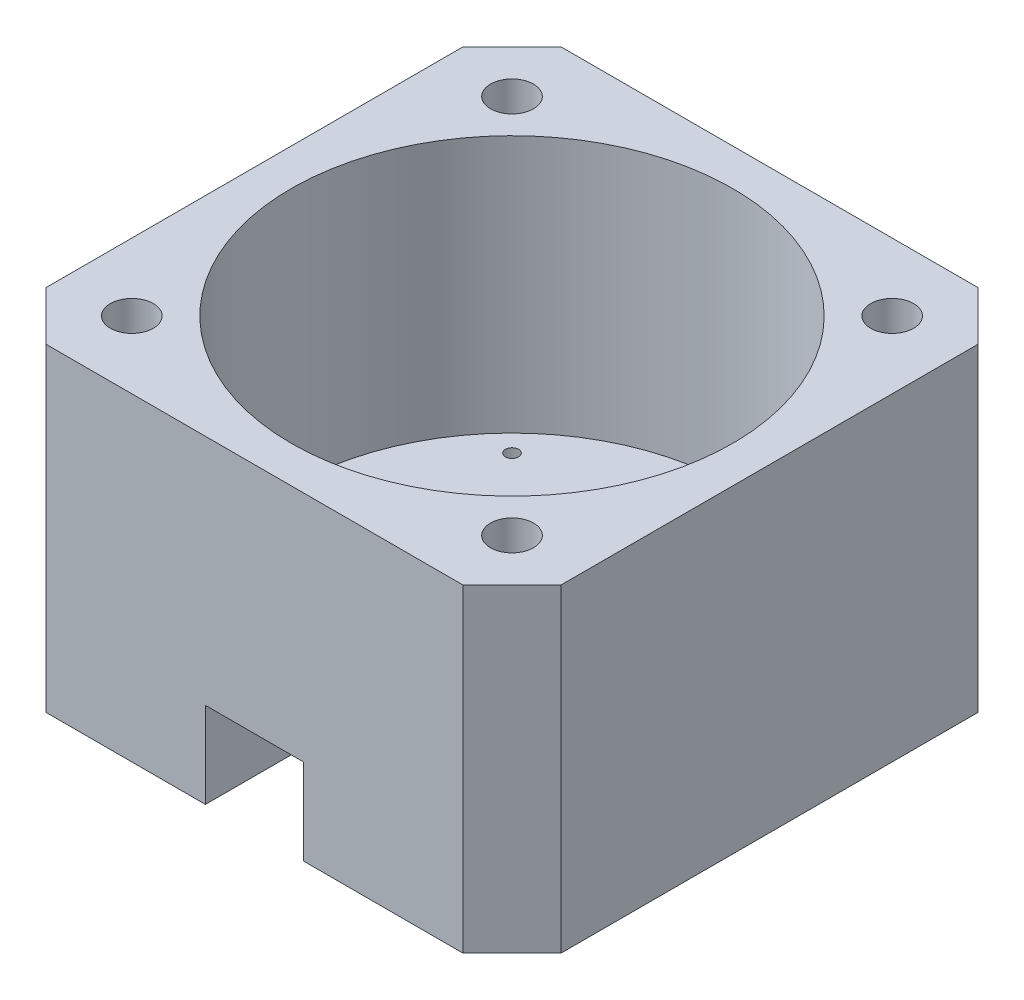
SolidWorks part; units mm, degrees
ref_plane "前视基准面" through (0, 0, 0) normal (0, 0, 1) x (1, 0, 0)
ref_plane "上视基准面" through (0, 0, 0) normal (0, 1, 0) x (1, 0, 0)
ref_plane "右视基准面" through (0, 0, 0) normal (1, 0, 0) x (0, 0, -1)
other "Configuration Table"
sketch "草图-尺寸参考" plane through (0, 0, 0) normal (0, 0, 1) x (1, 0, 0)
  line L1 (-6.8884, 24.2) -> (13.6066, 24.2) construction
  line L2 (-60.137, 0) -> (58.2604, 0) construction
  line L3 (-21, 20) -> (37.7214, 20) construction
  line L4 (-21, 20) -> (58.2604, 20) construction
  line L5 (-2.8262, 50) -> (1.944, 50) construction
  line L6 (-32.6672, 26) -> (36.6626, 26) construction
  line L7 (-40.6172, 32.8) -> (44.682, 32.8) construction
  line L8 (-21, 32.8) -> (58.2604, 32.8) construction
  line L9 (-21, 50) -> (58.2604, 50) construction
  line L10 (-40.6172, 5) -> (58.2604, 5) construction
  line L11 (-21, 26) -> (58.2604, 26) construction
  line L12 (15.1825, 29.4) -> (26.9517, 29.4) construction
  line L13 (-40.6172, 29.4) -> (26.9517, 29.4) construction
  line L14 (-40.6172, 32.8) -> (26.9517, 32.8) construction
  line L15 (-21, 24.2) -> (58.2604, 24.2) construction
  line L16 (2.984, 50.2) -> (7.9005, 50.2) construction
  line L17 (-6.8884, 50.2) -> (13.6066, 50.2) construction
  line L18 (7.3572, 26.2) -> (10.1879, 26.2) construction
  line L19 (15.1825, -0.6) -> (26.9517, -0.6) construction
  line L20 (-6.8884, 26.2) -> (13.6066, 26.2) construction
  line L21 (-21, 0) -> (58.2604, 0) construction
  line L22 (-60.137, 5) -> (58.2604, 5) construction
  dimension "D3" = 5
  dimension "D2" = 26
  dimension "D11" = 15
  dimension "D4" = 24
  dimension "D5" = 6.8
  dimension "D6" = 3.4
  dimension "D7" = 4.2
  dimension "D8" = 26
  dimension "D9" = 2
  dimension "D10" = 30
sketch "草图1" plane through (0, 0, 0) normal (0, 1, 0) x (1, 0, 0)
  line L0 (0, 64.5461) -> (0, -53.8448) construction
  line L1 (-21, -21) -> (21, -21)
  line L2 (-21, -21) -> (-21, 21)
  line L3 (-21, 21) -> (21, 21)
  line L4 (21, -21) -> (21, 21)
  line L5 (-21, -21) -> (21, 21) construction
  line L6 (-21, 21) -> (21, -21) construction
  line L7 (-56.9939, 0) -> (64.175, 0) construction
  line L8 (-15.5, 64.5461) -> (-15.5, -53.8448) construction
  line L9 (15.5, 64.5461) -> (15.5, -53.8448) construction
  line L10 (-56.9939, -15.5) -> (64.175, -15.5) construction
  line L11 (-56.9939, 15.5) -> (64.175, 15.5) construction
  circle A0 centre (-15.5, 15.5) radius 1.75
  circle A1 centre (15.5, 15.5) radius 1.75
  circle A2 centre (15.5, -15.5) radius 1.75
  circle A3 centre (-15.5, -15.5) radius 1.75
  circle A4 centre (0, 0.1912) radius 9.5 construction
  point P0 (0, 0)
  point P29 (0, 0)
  dimension "D7" = 3.5
  dimension "D9" = 19
  dimension "D1" = 42
  dimension "D2" = 42
  dimension "D3" = 15.5
  dimension "D4" = 15.5
  dimension "D5" = 15.5
  dimension "D6" = 15.5
  dimension "D8" = 4
extrude "凸台-拉伸1" add sketch "草图1" along normal blind 26
sketch "草图5" plane through (0, 0, 0) normal (0, -1, 0) x (1, 0, 0)
  line L0 (-21, -21) -> (21, 21) construction
  line L1 (-21, 21) -> (21, -21) construction
  line L3 (-21, -21) -> (21, 21) construction
  line L4 (-21, 21) -> (21, -21) construction
  circle A0 centre (0, -0.1912) radius 9.5 construction
  circle A1 centre (0, -0.1912) radius 9.5 construction
  point P3 (21, 21)
  point P37 (-6.6213, 6.6213)
  point P39 (6.6213, 6.6213)
  point P41 (6.8124, -6.8124)
  point P43 (-6.8124, -6.8124)
  point P49 (0, 0)
sketch "草图8" plane through (0, 0, 0) normal (0, -1, 0) x (1, 0, 0)
  circle A1 centre (0, 0) radius 6.5
  dimension "D1" = 13
extrude "切除-拉伸1" cut sketch "草图8" against normal through all
sketch "草图9" plane through (0, 0, 0) normal (0, -1, 0) x (1, 0, 0)
  line L0 (-21, 21) -> (21, -21) construction
  line L1 (-21, -21) -> (21, 21) construction
  line L2 (-21, 21) -> (21, -21) construction
  line L3 (-21, -21) -> (21, 21) construction
  circle A0 centre (0, 0) radius 16 construction
  point P12 (-11.3137, 11.3137)
  point P16 (11.3137, -11.3137)
  point P18 (11.3137, 11.3137)
  point P23 (-11.3137, -11.3137)
  dimension "D1" = 32
hole_wizard "Ø4.4 (4.4) 直径孔1" positions "草图9" profile "草图11" hole size "Ø4.4" standard "GB"
sketch "草图11" plane through (-11.3137, 0, -11.3137) normal (1, 0, 0) x (0, 0, -1)
  line L0 (0, 0) -> (0, 5.3219)
  line L1 (0, 5.3219) -> (2.2, 4)
  line L2 (2.2, 4) -> (2.2, 0)
  line L5 (2.2, 0) -> (0, 0)
  line L10 (0, 5.3219) -> (-2.2, 4) construction
  line L11 (0, -6.35) -> (0, 107.95) construction
  dimension "孔直径" = 4.4
  dimension "孔深度" = 4
  dimension "导头角度" = 118
sketch "草图13" plane through (0, 26, 0) normal (0, 1, 0) x (1, 0, 0)
  circle A0 centre (0, 0) radius 18
  dimension "D1" = 36
extrude "切除-拉伸2" cut sketch "草图13" against normal blind 21
chamfer "倒角1" distance 4 angle 45 4 edges at (-21, 13, 21) (21, 13, 21) (21, 13, -21) (-21, 13, -21)
sketch "草图14" plane through (0, 0, 0) normal (0, -1, 0) x (1, 0, 0)
  line L0 (0, -64.5461) -> (0, 53.8448) construction
  line L1 (-4, 23) -> (4, 23)
  line L2 (-4, 23) -> (-4, 13)
  line L3 (-4, 13) -> (4, 13)
  line L4 (4, 23) -> (4, 13)
  line L5 (-4, 23) -> (4, 13) construction
  line L6 (-4, 13) -> (4, 23) construction
  circle A0 centre (0, 0) radius 18 construction
  point P0 (0, 18)
  dimension "D1" = 8
  dimension "D2" = 10
extrude "切除-拉伸3" cut sketch "草图14" against normal blind 7
hole_wizard "M2.5 六角圆柱头螺钉的柱形沉头孔1" positions "草图5" profile "草图15" counterbore size "M2.5" standard "GB" end condition through all
sketch "草图15" plane through (-6.8124, 0, -6.8124) normal (1, 0, 0) x (0, 0, -1)
  line L0 (0, 0) -> (0, 26)
  line L1 (0, 26) -> (1.35, 26)
  line L3 (1.35, 26) -> (1.35, 2.5)
  line L4 (1.35, 2.5) -> (2.5, 2.5)
  line L5 (2.5, 2.5) -> (2.5, 0)
  line L7 (2.5, 0) -> (0, 0)
  line L11 (0, -6.35) -> (0, 107.95) construction
  dimension "通孔孔直径" = 2.7
  dimension "通孔孔深度" = 26
  dimension "柱形沉头孔直径" = 5
  dimension "柱形沉头孔深度" = 2.5
